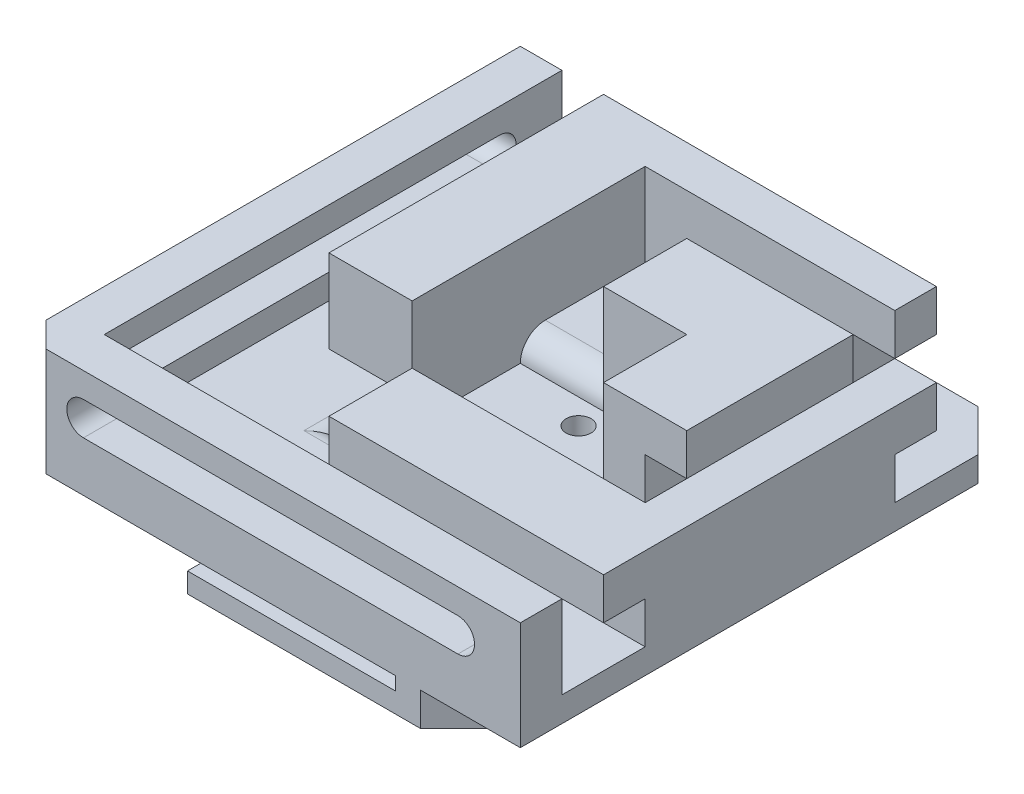
SolidWorks part; units mm, degrees
material "9400A光敏树脂"
ref_plane "前视基准面" through (0, 0, 0) normal (0, 0, 1) x (1, 0, 0)
ref_plane "上视基准面" through (0, 0, 0) normal (0, 1, 0) x (1, 0, 0)
ref_plane "右视基准面" through (0, 0, 0) normal (1, 0, 0) x (0, 0, -1)
other "Configuration Table"
sketch "草图2" plane through (0, 0, 0) normal (0, 1, 0) x (1, 0, 0)
  line L1 (-30, 30) -> (30, 30)
  line L2 (-30, 30) -> (-30, -30)
  line L3 (-30, -30) -> (30, -30)
  line L4 (30, 30) -> (30, -30)
  line L5 (-30, 30) -> (30, -30) construction
  line L6 (-30, -30) -> (30, 30) construction
  point P0 (0, 0)
  dimension "D1" = 60
  dimension "D2" = 60
extrude "凸台-拉伸1" add sketch "草图2" along normal blind 3
sketch "草图6" plane through (0, 0, 0) normal (0, 1, 0) x (1, 0, 0)
  line L1 (-7, 7) -> (7, 7) construction
  line L2 (-7, 7) -> (-7, -7) construction
  line L3 (-7, -7) -> (7, -7) construction
  line L4 (7, 7) -> (7, -7) construction
  line L5 (-7, 7) -> (7, -7) construction
  line L6 (-7, -7) -> (7, 7) construction
  circle A0 centre (0, -7) radius 1.5
  circle A1 centre (7, 0) radius 1.5
  circle A2 centre (0, 7) radius 1.5
  circle A3 centre (-7, 0) radius 1.5
  point P0 (0, 0)
  dimension "D3" = 3
  dimension "D4" = 3
  dimension "D5" = 3
  dimension "D6" = 3
  dimension "D1" = 14
  dimension "D2" = 14
extrude "切除-拉伸2" cut sketch "草图6" along normal up to surface (3 mm away) from surface at 0 up to face at (0, 3, 0) starting at face at (0, 0, 0)
sketch "草图7" plane through (0, 0, 0) normal (0, 0, 1) x (1, 0, 0)
  line L0 (0, -1000) -> (0, 49000) construction
  line L1 (-15, 3) -> (-15, 8)
  line L2 (-30, 3) -> (30, 3) construction
  line L3 (-15, 8) -> (-20, 8)
  line L4 (-20, 8) -> (-20, 13)
  line L5 (-20, 13) -> (-10, 13)
  line L6 (-10, 13) -> (-10, 3)
  line L7 (-10, 3) -> (-15, 3)
  line L9 (-30, 3) -> (-30, 0) construction
  line L10 (10, 3) -> (15, 3)
  line L11 (10, 13) -> (10, 3)
  line L12 (20, 13) -> (10, 13)
  line L13 (20, 8) -> (20, 13)
  line L14 (15, 8) -> (20, 8)
  line L15 (15, 3) -> (15, 8)
  dimension "D1" = 10
  dimension "D2" = 15
  dimension "D3" = 5
  dimension "D4" = 10
  dimension "D5" = 5
extrude "凸台-拉伸2" add sketch "草图7" along normal blind 30 from surface at -30 starting at face at (0, 1.5, -30)
sketch "草图8" plane through (0, 0, 0) normal (1, 0, 0) x (0, 0, -1)
  line L0 (0, -1000) -> (0, 49000) construction
  line L1 (-15, 3) -> (-15, 8)
  line L2 (-30, 3) -> (30, 3) construction
  line L3 (-15, 8) -> (-20, 8)
  line L4 (-20, 8) -> (-20, 13)
  line L5 (-20, 13) -> (-10, 13)
  line L6 (-10, 13) -> (-10, 3)
  line L7 (-10, 3) -> (-15, 3)
  line L8 (-30, 3) -> (-30, 0) construction
  line L9 (10, 3) -> (15, 3)
  line L10 (10, 13) -> (10, 3)
  line L11 (20, 13) -> (10, 13)
  line L12 (20, 8) -> (20, 13)
  line L13 (15, 8) -> (20, 8)
  line L14 (15, 3) -> (15, 8)
  dimension "D1" = 15
  dimension "D2" = 10
  dimension "D3" = 5
  dimension "D4" = 10
  dimension "D5" = 5
extrude "凸台-拉伸3" add sketch "草图8" against normal blind 30 from surface at 30 starting at face at (30, 1.5, 0)
sketch "草图9" plane through (0, 0, 0) normal (0, 1, 0) x (1, 0, 0)
  line L1 (30, 20) -> (20, 20)
  line L2 (30, 20) -> (30, 10)
  line L3 (30, 10) -> (20, 10)
  line L4 (20, 20) -> (20, 10)
  line L5 (10, 30) -> (20, 30)
  line L6 (10, 30) -> (10, 20)
  line L7 (10, 20) -> (20, 20)
  line L8 (20, 30) -> (20, 20)
extrude "切除-拉伸3" cut sketch "草图9" against normal up to surface (10 mm away) from surface at 13 contours L1 L4 L3 L2 | L8 L5 L6 L7 up to face at (22.5, 3, -22.5) starting at face at (15, 13, -15)
sketch "草图10" plane through (0, 0, 0) normal (0, 0, 1) x (1, 0, 0)
  line L1 (20, 8) -> (15, 8)
  line L2 (20, 8) -> (20, 3)
  line L3 (20, 3) -> (15, 3)
  line L4 (15, 8) -> (15, 3)
extrude "切除-拉伸4" cut sketch "草图10" along normal up to surface (5 mm away) from surface at -15 up to face at (17.5, 5.5, -10) starting at face at (17.5, 5.5, -15)
sketch "草图11" plane through (0, 0, 0) normal (1, 0, 0) x (0, 0, -1)
  line L0 (-10, 3) -> (30, 3) construction
  line L1 (20, 8) -> (15, 8)
  line L2 (20, 8) -> (20, 3)
  line L3 (20, 3) -> (15, 3)
  line L4 (15, 8) -> (15, 3)
  dimension "D1" = 5
extrude "切除-拉伸5" cut sketch "草图11" along normal up to surface (5 mm away) from surface at 10 up to face at (15, 5.5, -10) starting at face at (10, 5.5, -17.5)
sketch "草图16" plane through (0, 0, 0) normal (0, 1, 0) x (1, 0, 0)
  line L0 (-10, -25) -> (15, -25)
  line L1 (-30, -30) -> (-10, -30) construction
  line L2 (-30, -30) -> (-30, -10) construction
  line L3 (-30, -10) -> (-10, -10) construction
  line L4 (-10, -30) -> (-10, -10) construction
  line L5 (15, -25) -> (15, -30)
  line L6 (-30, -30) -> (30, -30) construction
  line L7 (15, -30) -> (18, -30)
  line L8 (18, -30) -> (18, -22)
  line L9 (18, -22) -> (-10, -22)
  line L10 (-10, -22) -> (-10, -25)
  line L11 (-707.1068, -707.1068) -> (34648.2323, 34648.2323) construction
  line L12 (-22, 18) -> (-22, -10)
  line L13 (-30, 18) -> (-22, 18)
  line L14 (-30, 15) -> (-30, 18)
  line L15 (-25, 15) -> (-30, 15)
  line L16 (-25, -10) -> (-25, 15)
  line L17 (-22, -10) -> (-25, -10)
  dimension "D1" = 20
  dimension "D2" = 20
  dimension "D3" = 25
  dimension "D4" = 5
  dimension "D5" = 3
  dimension "D6" = 3
extrude "凸台-拉伸5" add sketch "草图16" against normal blind 1.6
sketch "草图17" plane through (0, 0, 0) normal (0, 1, 0) x (1, 0, 0)
  line L0 (-30, -30) -> (15, -30) construction
  line L1 (18, -22) -> (-10, -22)
  line L2 (18, -22) -> (18, -30)
  line L3 (18, -30) -> (-10, -30)
  line L4 (-10, -22) -> (-10, -30)
  line L5 (-707.1068, -707.1068) -> (34648.2323, 34648.2323) construction
  line L6 (-30, 18) -> (-30, -10)
  line L7 (-22, -10) -> (-30, -10)
  line L8 (-22, 18) -> (-22, -10)
  line L9 (-22, 18) -> (-30, 18)
  dimension "D1" = 28
extrude "凸台-拉伸6" add sketch "草图17" against normal blind 2 from surface at -1.6 starting at face at (-25.6667, -1.6, -7.6667)
sketch "草图21" plane through (0, 0, 0) normal (0, 1, 0) x (1, 0, 0)
  circle A0 centre (0, 0) radius 12.5
  dimension "D1" = 25
extrude "凸台-拉伸8" add sketch "草图21" against normal blind 4
sketch "草图22" plane through (0, 0, 0) normal (0, 1, 0) x (1, 0, 0)
  circle A0 centre (7, 0) radius 1.5 construction
  circle A1 centre (0, -7) radius 1.5 construction
  circle A2 centre (-7, 0) radius 1.5 construction
  circle A3 centre (0, 7) radius 1.5 construction
  circle A4 centre (7, 0) radius 1.5
  circle A5 centre (0, -7) radius 1.5
  circle A6 centre (-7, 0) radius 1.5
  circle A7 centre (0, 7) radius 1.5
extrude "切除-拉伸6" cut sketch "草图22" against normal blind 4
sketch "草图23" plane through (0, 0, 0) normal (0, 1, 0) x (1, 0, 0)
  line L0 (-1000, 0) -> (49000, 0) construction
  line L1 (0, -1000) -> (0, 49000) construction
  line L2 (-30, -30) -> (15, -30) construction
  line L3 (18, -22) -> (-18, -22) construction
  line L4 (18, -22) -> (18, -30) construction
  line L5 (18, -30) -> (-18, -30) construction
  line L6 (-18, -22) -> (-18, -30) construction
  line L7 (-30, 15) -> (-30, -30) construction
  line L8 (-22, 18) -> (-30, 18) construction
  line L9 (-22, 18) -> (-22, -18) construction
  line L10 (-22, -18) -> (-30, -18) construction
  line L11 (-30, 18) -> (-30, -18) construction
  line L12 (18, 30) -> (-18, 30) construction
  line L13 (-18, 22) -> (-18, 30) construction
  line L14 (18, 22) -> (-18, 22) construction
  line L15 (18, 22) -> (18, 30) construction
  line L16 (22, -18) -> (30, -18) construction
  line L17 (30, 18) -> (30, -18) construction
  line L18 (22, 18) -> (30, 18) construction
  line L19 (22, 18) -> (22, -18) construction
  line L20 (22, -18) -> (18, -22)
  line L21 (-10, -22) -> (-22, -10)
  line L22 (18, 22) -> (22, 18)
  line L23 (-18, 22) -> (-22, 18)
  line L24 (-22, -10) -> (-22, 18)
  line L25 (22, -18) -> (30, -18)
  line L26 (30, -18) -> (30, 18)
  line L27 (30, 18) -> (22, 18)
  line L28 (18, 22) -> (18, 30)
  line L29 (18, 30) -> (-18, 30)
  line L30 (-18, 30) -> (-18, 22)
  line L31 (-10, -22) -> (18, -22)
  circle A0 centre (0, 7) radius 1.5 construction
  circle A1 centre (7, 0) radius 1.5 construction
  circle A2 centre (-7, 0) radius 1.5 construction
  circle A3 centre (0, -7) radius 1.5 construction
  circle A4 centre (0, 7) radius 1.5
  circle A5 centre (7, 0) radius 1.5
  circle A6 centre (-7, 0) radius 1.5
  circle A7 centre (0, -7) radius 1.5
  dimension "D1" = 36
  dimension "D2" = 36
extrude "凸台-拉伸9" add sketch "草图23" against normal blind 4
sketch "草图24" plane through (0, 0, 0) normal (0, 1, 0) x (1, 0, 0)
  line L0 (-30, -10) -> (-30, 18) construction
  line L1 (-30, 18) -> (-22, 18) construction
  line L2 (-22, 18) -> (-22, -10) construction
  line L3 (-22, -10) -> (-30, -10) construction
  line L4 (-10, -22) -> (18, -22) construction
  line L5 (18, -22) -> (18, -30) construction
  line L6 (18, -30) -> (-10, -30) construction
  line L7 (-10, -30) -> (-10, -22) construction
  line L8 (-30, -10) -> (-30, 18)
  line L9 (-30, 18) -> (-22, 18)
  line L10 (-22, 18) -> (-22, -10)
  line L11 (-22, -10) -> (-30, -10)
  line L12 (-10, -22) -> (18, -22)
  line L13 (18, -22) -> (18, -30)
  line L14 (18, -30) -> (-10, -30)
  line L15 (-10, -30) -> (-10, -22)
extrude "凸台-拉伸10" add sketch "草图24" against normal up to surface (0.4 mm away) from surface at -3.6 up to face at (7, -4, 1.5) starting at face at (-26, -3.6, -4)
sketch "草图25" plane through (0, 0, 0) normal (0, 1, 0) x (1, 0, 0)
  line L0 (-10, 0) -> (-10, 30) construction
  line L1 (-20, 0) -> (-10, 0)
  line L2 (-20, 0) -> (-20, -3)
  line L3 (-20, -3) -> (-10, -3)
  line L4 (-10, 0) -> (-10, -3)
  line L5 (0, -20) -> (30, -20) construction
  line L6 (0, -10) -> (-3, -10)
  line L7 (0, -10) -> (0, -20)
  line L8 (0, -20) -> (-3, -20)
  line L9 (-3, -10) -> (-3, -20)
  dimension "D1" = 3
  dimension "D2" = 3
extrude "凸台-拉伸11" add sketch "草图25" along normal up to surface (10 mm away) from surface at 3 up to face at (-15, 13, -15) starting at face at (0.8333, 3, -0.8333)
sketch "草图26" plane through (0, 0, 0) normal (0, 1, 0) x (1, 0, 0)
  line L0 (-30, -30) -> (30, -30) construction
  line L1 (-30, 30) -> (-25, 30)
  line L2 (-30, 30) -> (-30, -30)
  line L3 (-30, -30) -> (-25, -30)
  line L4 (-25, 30) -> (-25, -30)
  line L6 (30, -30) -> (-30, -30)
  line L7 (30, -30) -> (30, -25)
  line L8 (30, -25) -> (-30, -25)
  line L9 (-30, -30) -> (-30, -25)
  dimension "D1" = 5
  dimension "D2" = 5
extrude "凸台-拉伸12" add sketch "草图26" along normal blind 10 from surface at 3 contours L7 L8 L4 L6 | L8 L4 L1 L2 | L4 L8 L2 L3 starting at face at (-2.25, 3, 2.25)
sketch "草图27" plane through (0, 0, 0) normal (1, 0, 0) x (0, 0, -1)
  line L0 (0, 13) -> (0, 8) construction
  line L1 (-30, 13) -> (30, 13) construction
  line L2 (22.5, 8) -> (-22.5, 8) construction
  line L3 (22.5, 6) -> (-22.5, 6)
  line L4 (22.5, 10) -> (-22.5, 10)
  arc A0 (22.5, 6) -> (22.5, 10) centre (22.5, 8) ccw
  arc A1 (-22.5, 10) -> (-22.5, 6) centre (-22.5, 8) ccw
  point P7 (0, 8)
  dimension "D2" = 2
  dimension "D1" = 5
  dimension "D3" = 45
extrude "切除-拉伸7" cut sketch "草图27" along normal up to surface (5 mm away) from surface at -30 up to face at (-25, 8, -2.5) starting at face at (-30, 1.48, -4.6)
sketch "草图28" plane through (0, 0, 0) normal (0, 0, 1) x (1, 0, 0)
  line L0 (0, 13) -> (0, 8) construction
  line L1 (-30, 13) -> (30, 13) construction
  line L2 (-22.5, 8) -> (22.5, 8) construction
  line L3 (-22.5, 10) -> (22.5, 10)
  line L4 (-22.5, 6) -> (22.5, 6)
  arc A0 (-22.5, 10) -> (-22.5, 6) centre (-22.5, 8) ccw
  arc A1 (22.5, 6) -> (22.5, 10) centre (22.5, 8) ccw
  point P7 (0, 8)
  dimension "D3" = 2
  dimension "D1" = 5
  dimension "D2" = 45
extrude "切除-拉伸8" cut sketch "草图28" against normal up to surface (5 mm away) from surface
sketch "草图31" plane through (0, 0, 0) normal (0, 1, 0) x (1, 0, 0)
  line L0 (-10, -10) -> (-30, -30) construction
  line L1 (-30, -30) -> (-10, -30) construction
  line L2 (-30, -30) -> (-30, -10) construction
  line L3 (-30, -10) -> (-10, -10) construction
  line L4 (-10, -30) -> (-10, -10) construction
  circle A0 centre (-20, -20) radius 1
  dimension "D3" = 2
  dimension "D1" = 20
  dimension "D2" = 20
extrude "切除-拉伸10" cut sketch "草图31" against normal up to surface (3 mm away) from surface at 3 up to face at (-13.5556, 0, 13.5556) starting at face at (-1.625, 3, 1.625)
sketch "草图32" plane through (0, 0, 0) normal (0, 1, 0) x (1, 0, 0)
  line L0 (30, 30) -> (30, 25)
  line L1 (30, -10) -> (30, 30) construction
  line L2 (30, 25) -> (25, 30)
  line L3 (30, 30) -> (-10, 30) construction
  line L4 (25, 30) -> (30, 30)
  dimension "D1" = 5
  dimension "D2" = 5
extrude "切除-拉伸11" cut sketch "草图32" along normal blind 4
sketch "草图33" plane through (0, 0, 0) normal (0, 1, 0) x (1, 0, 0)
  line L0 (-30, -30) -> (-27, -30)
  line L1 (-30, -30) -> (30, -30) construction
  line L2 (-27, -30) -> (-30, -27)
  line L3 (-30, -30) -> (-30, 30) construction
  line L4 (-30, -27) -> (-30, -30)
  dimension "D1" = 3
  dimension "D2" = 3
extrude "切除-拉伸12" cut sketch "草图33" along normal up to surface (13 mm away) up to face at (-8.3333, 13, 8.3333)
sketch "草图34" plane through (0, 0, 0) normal (0, 1, 0) x (1, 0, 0)
  line L1 (-10, -10) -> (10, -10)
  line L2 (-10, -10) -> (-10, 10)
  line L3 (-10, 10) -> (10, 10)
  line L4 (10, -10) -> (10, 10)
  line L5 (-10, -10) -> (10, 10) construction
  line L6 (-10, 10) -> (10, -10) construction
  point P0 (0, 0)
extrude "切除-拉伸14" cut sketch "草图34" against normal blind 3 from surface at 3 starting at face at (-20, 3, 21)
sketch "草图35" plane through (0, 0, 0) normal (1, 0, 0) x (0, 0, -1)
  line L0 (-10, 3) -> (25, 3) construction
  line L1 (-10, 13) -> (10, 13)
  line L2 (-10, 13) -> (-10, 3)
  line L3 (-10, 3) -> (10, 3)
  line L4 (10, 13) -> (10, 3)
  dimension "D1" = 20
extrude "凸台-拉伸14" add sketch "草图35" against normal blind 5 from surface at 30 starting at face at (30, 4.5, 9.375)
sketch "草图36" plane through (0, 0, 0) normal (0, 0, 1) x (1, 0, 0)
  line L0 (0, 13) -> (20, 13) construction
  line L1 (-10, 3) -> (10, 3)
  line L2 (-10, 3) -> (-10, 13)
  line L3 (-10, 13) -> (10, 13)
  line L4 (10, 3) -> (10, 13)
  dimension "D1" = 20
extrude "凸台-拉伸15" add sketch "草图36" along normal blind 5 from surface at -30 starting at face at (-9.375, 4.5, -30)
sketch "草图37" plane through (0, 0, 0) normal (0, 0, 1) x (1, 0, 0)
  line L0 (10, 3) -> (10, 13)
  line L1 (10, 13) -> (20, 13)
  line L2 (20, 13) -> (20, 8)
  line L3 (20, 8) -> (15, 8)
  line L4 (0, 8) -> (20, 8) construction
  line L5 (15, 8) -> (15, 3)
  line L6 (15, 3) -> (10, 3)
  line L7 (0, 8) -> (15, 8) construction
extrude "凸台-拉伸16" add sketch "草图37" along normal blind 5 from surface at -30 starting at face at (-6.875, 4.5, -30)
sketch "草图38" plane through (0, 0, 0) normal (1, 0, 0) x (0, 0, -1)
  line L0 (10, 13) -> (20, 13)
  line L1 (20, 13) -> (20, 8)
  line L2 (0, 13) -> (20, 13) construction
  line L3 (20, 8) -> (15, 8)
  line L4 (15, 8) -> (15, 3)
  line L5 (15, 3) -> (10, 3)
  line L6 (10, 3) -> (10, 13)
extrude "凸台-拉伸18" add sketch "草图38" against normal blind 5 from surface at 30 starting at face at (30, 4.5, 6.875)
sketch "草图40" plane through (0, 0, 0) normal (0, 1, 0) x (1, 0, 0)
  line L0 (-30, 18) -> (-18, 30)
  line L1 (-18, 30) -> (-18, 22)
  line L2 (-18, 22) -> (-22, 18)
  line L3 (-22, 18) -> (-30, 18)
  line L4 (18, 30) -> (30, 18)
  line L5 (30, 18) -> (22, 18)
  line L6 (22, 18) -> (18, 22)
  line L7 (18, 22) -> (18, 30)
  line L8 (30, -18) -> (18, -30)
  line L9 (18, -30) -> (18, -22)
  line L10 (18, -22) -> (22, -18)
  line L11 (22, -18) -> (30, -18)
extrude "凸台-拉伸19" add sketch "草图40" against normal blind 4
sketch "草图41" plane through (0, 0, 0) normal (0, 0, 1) x (1, 0, 0)
  line L0 (30, 0) -> (26, -4)
  line L1 (18, -4) -> (30, -4) construction
  line L2 (26, -4) -> (30, -4)
  line L3 (30, -4) -> (30, 0)
  dimension "D1" = 4
extrude "切除-拉伸15" cut sketch "草图41" against normal up to surface (36 mm away) from surface
sketch "草图42" plane through (0, 0, 0) normal (1, 0, 0) x (0, 0, -1)
  line L0 (30, -4) -> (30, 0)
  line L1 (30, -4) -> (26, -4)
  line L2 (26, -4) -> (30, 0)
  dimension "D1" = 4
extrude "切除-拉伸16" cut sketch "草图42" along normal up to surface (36 mm away) from surface
fillet "圆角1" radius 5 1 edges at (24, 0, -24)
fillet "圆角2" radius 3 4 edges at (-6.5, 3, 10) (-10, 3, 6.5) (-5, 3, -10) (10, 3, 5)
